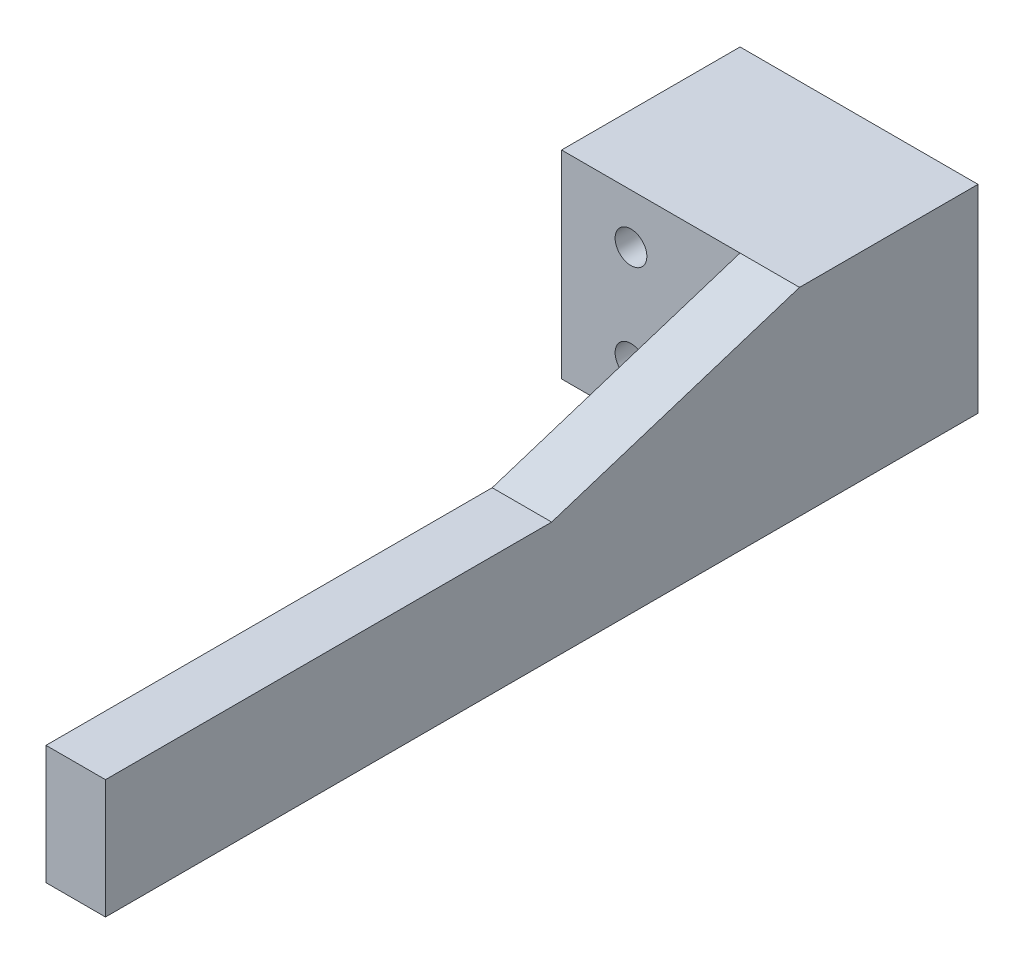
SolidWorks part; units mm, degrees
ref_plane "Front Plane" through (0, 0, 0) normal (0, 0, 1) x (1, 0, 0)
ref_plane "Top Plane" through (0, 0, 0) normal (0, 1, 0) x (1, 0, 0)
ref_plane "Right Plane" through (0, 0, 0) normal (1, 0, 0) x (0, 0, -1)
sketch "Sketch1" plane through (0, 0, 0) normal (0, 0, 1) x (1, 0, 0)
  line L1 (-12, -10) -> (12, -10)
  line L2 (-12, -10) -> (-12, 10)
  line L3 (-12, 10) -> (12, 10)
  line L4 (12, -10) -> (12, 10)
  line L5 (-12, -10) -> (12, 10) construction
  line L6 (-12, 10) -> (12, -10) construction
  circle A0 centre (-5, 5) radius 1.6
  circle A1 centre (-5, -5) radius 1.6
  point P0 (0, 0)
  point P10 (0, 0)
  point P11 (5, -5)
  dimension "D6" = 3.2
  dimension "D7" = 3.2
  dimension "D1" = 24
  dimension "D2" = 20
  dimension "D3" = 10
  dimension "D4" = 5
  dimension "D5" = 7
extrude "Boss-Extrude1" add sketch "Sketch1" along normal blind 18
sketch "Sketch2" plane through (12, 0, 0) normal (1, 0, 0) x (0, 0, -1)
  line L0 (-18, -10) -> (-18, 10) construction
  line L1 (-18, 2) -> (-88, 2)
  line L2 (-18, 2) -> (-18, -10)
  line L3 (-18, -10) -> (-88, -10)
  line L4 (-88, 2) -> (-88, -10)
  line L5 (-18, -10) -> (0, -10) construction
  line L6 (-18, 10) -> (-43, 2)
  line M6 (-18, 10) -> (-18, -10)
  dimension "D1" = 70
  dimension "D2" = 12
  dimension "D3" = 25
extrude "Boss-Extrude2" add sketch "Sketch2" against normal blind 6 contours L6 L1 M6 | L1 L4 L3 L2 region at (12, 4.6667, 26.3333)
ref_plane "Plane1" through (0, -7.5, 0) normal (0, -1, 0) x (-1, 0, 0)
sketch "Sketch3" plane through (0, -7.5, 0) normal (0, -1, 0) x (-1, 0, 0)
  line L0 (-6, -18) -> (-6, -88) construction
  line L1 (-6, -88) -> (-12, -88) construction
  line L2 (12, -9) -> (25.0759, -9) construction
  line L3 (12, -18) -> (12, 0) construction
  circle A0 centre (-6, -83) radius 2.5
  circle A1 centre (-6, -65) radius 2.5
  circle A2 centre (40.6396, -74) radius 45 construction
  point P8 (-9, -88)
  point P15 (28.1044, -74)
  point P16 (0, 0)
  dimension "D1" = 5
  dimension "D2" = 5
  dimension "D3" = 5
  dimension "D5" = 90
  dimension "D4" = 65
extrude "Boss-Extrude3" add sketch "Sketch3" against normal blind 7
fillet "Fillet1" radius 1 4 edges at (6, -4, 85.5) (6, -4, 80.5) (6, -4, 67.5) (6, -4, 62.5)
chamfer "Chamfer1" distance 2.5 angle 45 4 edges at (6, -7.5, 83) (6, -7.5, 65) (6, -0.5, 65) (6, -0.5, 83)
